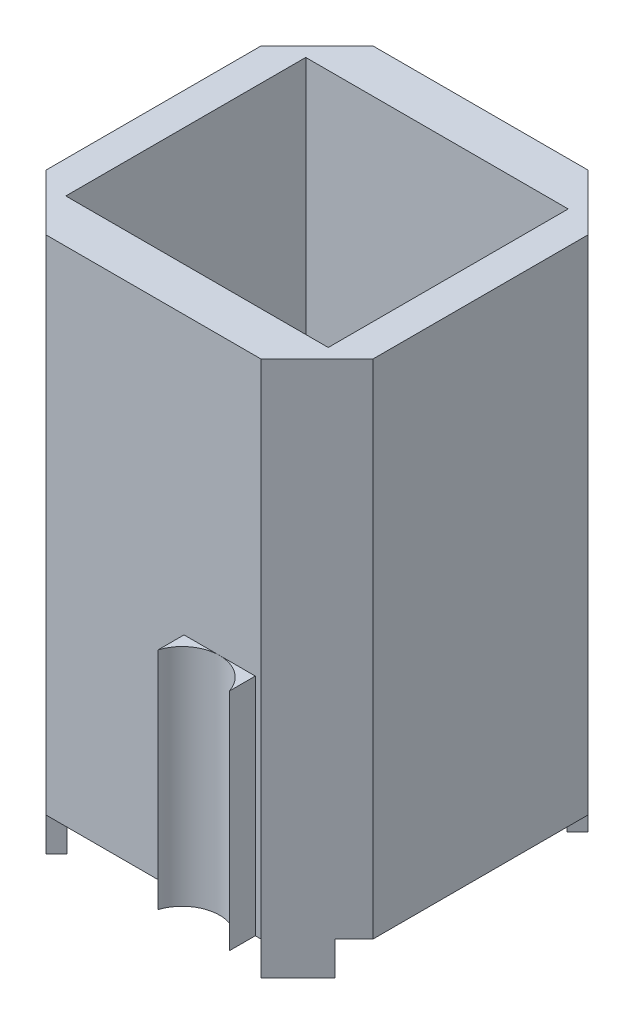
SolidWorks part; units mm, degrees
ref_plane "Front" through (0, 0, 0) normal (0, 0, 1) x (1, 0, 0)
ref_plane "Top" through (0, 0, 0) normal (0, 1, 0) x (1, 0, 0)
ref_plane "Right" through (0, 0, 0) normal (1, 0, 0) x (0, 0, -1)
sketch "Эскиз1" plane through (0, 0, 0) normal (0, 1, 0) x (1, 0, 0)
  line L0 (-17.9986, 18.1413) -> (-14.3288, 21.8112)
  line L1 (-17.5, 16) -> (17.5, 16)
  line L2 (-17.5, 16) -> (-17.5, -16)
  line L3 (-17.5, -16) -> (17.5, -16)
  line L4 (17.5, 16) -> (17.5, -16)
  line L5 (-17.5, 16) -> (17.5, -16) construction
  line L6 (-17.5, -16) -> (17.5, 16) construction
  line L7 (-17.9986, 18.1413) -> (17.9986, 18.1413)
  line L8 (-17.9986, 18.1413) -> (-17.9986, -18.1413)
  line L9 (-17.9986, -18.1413) -> (17.9986, -18.1413)
  line L10 (17.9986, 18.1413) -> (17.9986, -18.1413)
  line L11 (-17.9986, 18.1413) -> (17.9986, -18.1413) construction
  line L12 (-17.9986, -18.1413) -> (17.9986, 18.1413) construction
  line L13 (-17.9986, 18.1413) -> (-21.8099, 14.33)
  line L14 (17.9986, 18.1413) -> (14.3288, 21.8112)
  line L15 (21.8099, 14.33) -> (17.9986, 18.1413)
  line L16 (17.9986, -18.1413) -> (21.8099, -14.33)
  line L17 (17.9986, -18.1413) -> (14.3288, -21.8112)
  line L18 (-17.9986, -18.1413) -> (-14.3288, -21.8112)
  line L19 (-17.9986, -18.1413) -> (-21.8099, -14.33)
  line L20 (-14.3288, 21.8112) -> (14.3288, 21.8112)
  line L21 (21.8099, 14.33) -> (21.8099, -14.33)
  line L22 (14.3288, -21.8112) -> (-14.3288, -21.8112)
  line L23 (-21.8099, -14.33) -> (-21.8099, 14.33)
  point P0 (0, 0)
  point P6 (0, 0)
  point P18 (0, 0)
  point P20 (0, 0)
  dimension "D1" = 35
  dimension "D2" = 32
  dimension "D3" = 51.11
  dimension "D4" = 90
  dimension "D5" = 10.58
  dimension "D6" = 10.58
  dimension "D7" = 5.19
  dimension "D8" = 28.66
  dimension "D9" = 10.58
  dimension "D10" = 10.58
  dimension "D11" = 90
extrude "Бобышка-Вытянуть1" add sketch "Эскиз1" along normal blind 65 contours L20 L0 L7 L14 | L10 L7 L8 L9 L1 L4 L3 L2 | L23 L19 L8 L13 | L22 L17 L9 L18 | L21 L15 L10 L16 region at (0, 0, -19.9068) region at (0, 0, -17.6302) region at (-19.8297, 0, 0) region at (19.8297, 0, 0) region at (0, 0, 19.9068)
extrude "Бобышка-Вытянуть2" add sketch "Эскиз1<3>" against normal blind 2 contours L4 L1 L2 L3 | L23 L19 L8 L13 | L10 L7 L8 L9 L1 L4 L3 L2 | L20 L0 L7 L14 | L21 L15 L10 L16 | L22 L17 L9 L18 region at (0, 0, -19.9068) region at (0, 0, -17.6302) region at (-19.8297, 0, 0) region at (19.8297, 0, 0) region at (0, 0, 19.9068) region at (0, 0, 0)
sketch "Эскиз1<3>" plane through (0, 0, 0) normal (0, 1, 0) x (1, 0, 0) same geometry as "Эскиз1"
sketch "Эскиз2" plane through (0, -2, 0) normal (0, -1, 0) x (1, 0, 0)
  line L1 (-21.8099, 14.33) -> (-21.8099, -14.33) construction
  circle A0 centre (-3.8099, 8) radius 1
  circle A1 centre (-3.8099, -8) radius 1
  dimension "D1" = 2
  dimension "D2" = 2
  dimension "D3" = 16
  dimension "D4" = 8
  dimension "D5" = 18
  dimension "D6" = 18
extrude "Вырез-Вытянуть1" cut sketch "Эскиз2" against normal through all
sketch "Эскиз3" plane through (0, 0, 0) normal (0, 1, 0) x (1, 0, 0)
  circle A0 centre (-3.8099, 8) radius 2
  circle A1 centre (-3.8099, -8) radius 2
  dimension "D1" = 4
  dimension "D2" = 4
extrude "Вырез-Вытянуть2" cut sketch "Эскиз3" against normal blind 1
sketch "Эскиз4" plane through (0, -2, 0) normal (0, -1, 0) x (1, 0, 0)
  line L0 (-19.2785, 16.8614) -> (-14.3288, 21.8112)
  line L1 (-21.8099, 14.33) -> (-14.3288, 21.8112) construction
  line L2 (-14.3288, 21.8112) -> (-12.9145, 20.397)
  line L3 (-12.9145, 20.397) -> (-17.8643, 15.4472)
  line L4 (14.3288, 21.8112) -> (-14.3288, 21.8112) construction
  line L5 (0, 21.8112) -> (0, -21.8112)
  line L6 (-14.3288, -21.8112) -> (14.3288, -21.8112) construction
  line L7 (-17.8643, 15.4472) -> (-19.2785, 16.8614)
  line L8 (14.3288, 21.8112) -> (12.9145, 20.397)
  line L9 (21.8099, 14.33) -> (14.3288, 21.8112) construction
  line L10 (12.9145, 20.397) -> (17.8643, 15.4472)
  line L11 (-21.8099, 0) -> (21.8099, 0)
  line L12 (-21.8099, 14.33) -> (-21.8099, -14.33) construction
  line L13 (21.8099, -14.33) -> (21.8099, 14.33) construction
  line L14 (17.8643, 15.4472) -> (19.2785, 16.8614)
  line L15 (19.2785, 16.8614) -> (14.3288, 21.8112)
  line L16 (14.3288, -21.8112) -> (19.2785, -16.8614)
  line L17 (21.8099, -14.33) -> (14.3288, -21.8112) construction
  line L18 (19.2785, -16.8614) -> (17.8643, -15.4472)
  line L19 (17.8643, -15.4472) -> (12.9145, -20.397)
  line L20 (12.9145, -20.397) -> (14.3288, -21.8112)
  line L21 (-19.2785, -16.8614) -> (-14.3288, -21.8112)
  line L22 (-14.3288, -21.8112) -> (-21.8099, -14.33) construction
  line L23 (-14.3288, -21.8112) -> (-12.9145, -20.397)
  line L24 (-12.9145, -20.397) -> (-17.8643, -15.4472)
  line L25 (-17.8643, -15.4472) -> (-19.2785, -16.8614)
  line M3 (21.8099, 14.33) -> (14.3288, 21.8112)
  line M5 (-14.3288, 21.8112) -> (-21.8099, 14.33)
  line M7 (-21.8099, -14.33) -> (-14.3288, -21.8112)
  line M9 (14.3288, -21.8112) -> (21.8099, -14.33)
  dimension "D1" = 2
  dimension "D2" = 7
  dimension "D3" = 0
  dimension "D4" = 7
  dimension "D5" = 2
  dimension "D6" = 0
  dimension "D7" = 7
  dimension "D8" = 2
  dimension "D9" = 0
  dimension "D10" = 7
  dimension "D11" = 2
  dimension "D12" = 0
extrude "Бобышка-Вытянуть3" add sketch "Эскиз4" along normal blind 4.5 contours L10 L14 L8 M3 | L7 L3 L2 M5 | L24 L25 L23 M7 | L19 L20 L18 M9 region at (-16.0965, -2, 18.6292) region at (16.0965, -2, 18.6292) region at (16.0965, -2, -18.6292) region at (-16.0965, -2, -18.6292)
sketch "Эскиз5" plane through (0, -2, 0) normal (0, -1, 0) x (1, 0, 0)
  line L0 (14.3288, 21.8112) -> (-14.3288, 21.8112) construction
  line L1 (4.0751, 25.2612) -> (4.0751, 21.8112)
  line L2 (4.0751, 21.8112) -> (8.8288, 21.8112)
  line L3 (8.8288, 21.8112) -> (13.5824, 21.8112)
  line L4 (13.5824, 21.8112) -> (13.5824, 25.2612)
  arc A0 (4.0751, 25.2612) -> (13.5824, 25.2612) centre (8.8288, 26.8112) ccw
  line M12 (14.3288, 21.8112) -> (-14.3288, 21.8112)
  dimension "D1" = 10
  dimension "D2" = 5.5
  dimension "D3" = 5
  dimension "D6" = 3.45
  dimension "D7" = 3.45
extrude "Бобышка-Вытянуть4" add sketch "Эскиз5" against normal blind 30 contours A0 L1 M12 | A0 L4 M12 region at (5.1679, -2, 22.7323) region at (12.4896, -2, 22.7323)
